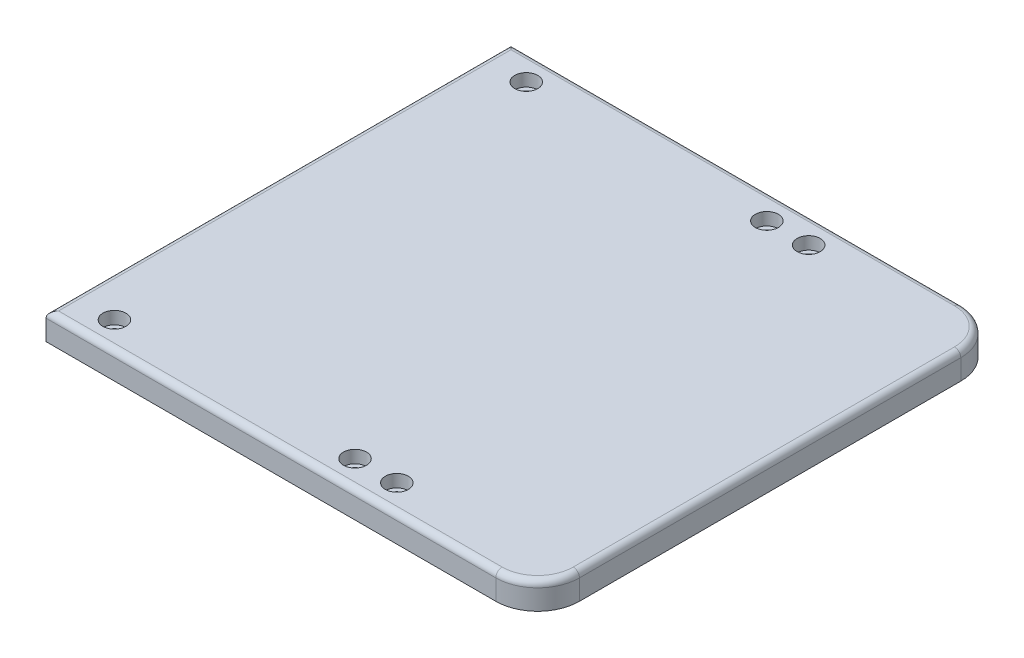
SolidWorks part; units mm, degrees
ref_plane "Front Plane" through (0, 0, 0) normal (0, 0, 1) x (1, 0, 0)
ref_plane "Top Plane" through (0, 0, 0) normal (0, 1, 0) x (1, 0, 0)
ref_plane "Right Plane" through (0, 0, 0) normal (1, 0, 0) x (0, 0, -1)
sketch "Sketch2" plane through (0, 0, 0) normal (0, 1, 0) x (1, 0, 0)
  line L1 (-117.5, 111.125) -> (117.5, 111.125)
  line L2 (-117.5, 111.125) -> (-117.5, -111.125)
  line L3 (-117.5, -111.125) -> (117.5, -111.125)
  line L4 (117.5, 111.125) -> (117.5, -111.125)
  line L5 (-117.5, 111.125) -> (117.5, -111.125) construction
  line L6 (-117.5, -111.125) -> (117.5, 111.125) construction
  point P0 (0, 0)
  dimension "D2" = 222.25
  dimension "D1" = 235
extrude "Boss-Extrude1" add sketch "Sketch2" along normal blind 12.7
fillet "Fillet6" radius 20 2 edges at (117.5, 6.35, -111.125) (117.5, 6.35, 111.125)
fillet "Fillet5" radius 3 6 edges at (-10, 12.7, 111.125) (-117.5, 12.7, 0) (-10, 12.7, -111.125) (117.5, 12.7, 0) (111.6421, 12.7, 105.2671) (111.6421, 12.7, -105.2671)
sketch "Sketch4" plane through (0, 12.7, 0) normal (0, 1, 0) x (1, 0, 0)
  line L0 (0, 0) -> (-45.9035, 0) construction
  line L1 (0, 0) -> (0, -26.5712) construction
  line L2 (97.5, -111.125) -> (-117.5, -111.125) construction
  line L3 (-117.5, -111.125) -> (-117.5, 111.125) construction
  line L4 (117.5, 91.125) -> (117.5, -91.125) construction
  point P0 (-97.5, -98.425)
  point P9 (17.5, 98.425)
  point P10 (37.5, -98.425)
  point P13 (37.5, 98.425)
  point P14 (-97.5, 98.425)
  point P21 (17.5, -98.425)
  dimension "D1" = 12.7
  dimension "D2" = 20
  dimension "D3" = 80
  dimension "D4" = 20
hole_wizard "CBORE for M6 SHCS1" positions "Sketch5" profile "Sketch6" counterbore size "M6" standard "ANSI Metric" end condition up to next
sketch "Sketch5" plane through (0, 12.7, 0) normal (0, 1, 0) x (1, 0, 0)
  point P0 (-97.5, -98.425)
  point P3 (37.5, -98.425)
  point P6 (37.5, 98.425)
  point P9 (-97.5, 98.425)
  point P12 (17.5, -98.425)
  point P15 (17.5, 98.425)
sketch "Sketch6" plane through (-97.5, 12.7, 98.425) normal (1, 0, 0) x (0, 0, 1)
  line L0 (0, 0) -> (0, 12.7)
  line L1 (0, 12.7) -> (3.3, 12.7)
  line L3 (3.3, 12.7) -> (3.3, 6)
  line L4 (3.3, 6) -> (5.5, 6)
  line L5 (5.5, 6) -> (5.5, 0)
  line L7 (5.5, 0) -> (0, 0)
  line L11 (0, -6.35) -> (0, 107.95) construction
  dimension "Thru Hole Dia." = 6.6
  dimension "Thru Hole Depth" = 12.7
  dimension "C'Bore Dia." = 11
  dimension "C'Bore Depth" = 6
equation "\"Length\"=250"
equation "\"Width\"=222.25"
equation "\"D2@Sketch2\"=\"Width\""
